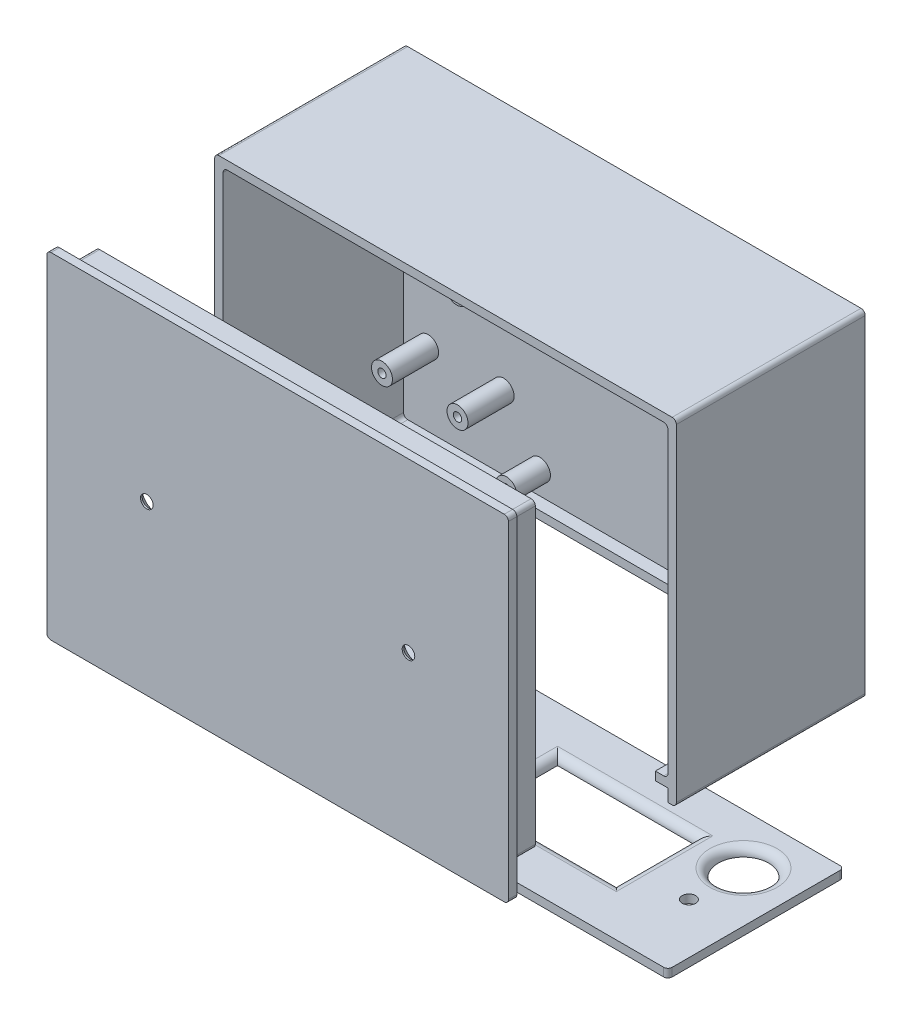
SolidWorks part; units mm, degrees
ref_plane "Спереди" through (0, 0, 0) normal (0, 0, 1) x (1, 0, 0)
ref_plane "Сверху" through (0, 0, 0) normal (0, 1, 0) x (1, 0, 0)
ref_plane "Справа" through (0, 0, 0) normal (1, 0, 0) x (0, 0, -1)
sketch "Эскиз1" plane through (0, 0, 0) normal (0, 0, 1) x (1, 0, 0)
  line L0 (-55, -41.511) -> (-53, -41.511)
  line L2 (-55, 38.489) -> (-55, -41.511)
  line L5 (-55, 38.489) -> (55, 38.489)
  line L6 (53, -36.511) -> (53, 36.489)
  line L7 (-53, -41.511) -> (-53, -38.511)
  line L8 (-53, -38.511) -> (-50, -38.511)
  line L9 (-50, -38.511) -> (-50, -36.511)
  line L10 (-50, -36.511) -> (-53, -36.511)
  line L11 (-53, -36.511) -> (-53, 36.489)
  line L12 (-53, 36.489) -> (53, 36.489)
  line L13 (0, 55.7111) -> (0, -96.3987) construction
  line L14 (50, -36.511) -> (53, -36.511)
  line L15 (50, -38.511) -> (50, -36.511)
  line L16 (53, -38.511) -> (50, -38.511)
  line L17 (53, -41.511) -> (53, -38.511)
  line L18 (55, 38.489) -> (55, -41.511)
  line L19 (55, -41.511) -> (53, -41.511)
  point P0 (0, 0)
  point P15 (0, 36.489)
  point P21 (0, 38.489)
  dimension "D1" = 2
  dimension "D2" = 2
  dimension "D3" = 2
  dimension "D4" = 55
  dimension "D5" = 80
  dimension "D6" = 2
  dimension "D7" = 3
  dimension "D8" = 3
extrude "Бобышка-Вытянуть3" add sketch "Эскиз1" along normal blind 43
sketch "Эскиз2" plane through (0, 0, 0) normal (0, 0, -1) x (-1, 0, 0)
  line L36 (55, 38.489) -> (55, -41.511) construction
  line L37 (-55, 38.489) -> (55, 38.489) construction
  line L38 (-55, -41.511) -> (-55, 38.489) construction
  line L39 (55, 38.489) -> (55, -41.511)
  line L40 (-55, 38.489) -> (55, 38.489)
  line L41 (-55, -41.511) -> (-55, 38.489)
  line L42 (-55, -41.511) -> (55, -41.511)
extrude "Бобышка-Вытянуть4" add sketch "Эскиз2" along normal blind 2
ref_plane "Плоскость1" through (0, 0, 8) normal (0, 0, 1) x (1, 0, 0)
sketch "Эскиз3" plane through (0, 0, 8) normal (0, 0, 1) x (1, 0, 0)
  line L0 (-53, -38.511) -> (-50, -38.511) construction
  line L1 (48, -32.511) -> (-23, -32.511) construction
  line L2 (48, -32.511) -> (48, 17.489) construction
  line L3 (48, 17.489) -> (-23, 17.489) construction
  line L4 (-23, -32.511) -> (-23, 17.489) construction
  line L5 (-33.1063, -7.511) -> (53.7568, -7.511) construction
  line L6 (12.5, 27.0434) -> (12.5, -35.2357) construction
  line L8 (50, -38.511) -> (53, -38.511) construction
  line L9 (53, 36.489) -> (53, -36.511) construction
  line L10 (-38.1409, 10.489) -> (-38.1409, -27.511) construction
  line L11 (-49.1409, 10.489) -> (-27.1409, 10.489) construction
  line L12 (-49.1409, 10.489) -> (-49.1409, -27.511) construction
  line L13 (-49.1409, -27.511) -> (-27.1409, -27.511) construction
  line L14 (-27.1409, 10.489) -> (-27.1409, -27.511) construction
  circle A0 centre (-20.5, 15.989) radius 1
  circle A1 centre (-20.5, 15.989) radius 2.5
  circle A2 centre (45.5, 15.989) radius 2.5
  circle A3 centre (45.5, 15.989) radius 1
  circle A4 centre (-20.5, 15.989) radius 1
  circle A5 centre (-20.5, 15.989) radius 2.5
  circle A6 centre (45.5, 15.989) radius 2.5
  circle A7 centre (45.5, 15.989) radius 1
  circle A8 centre (45.5, -31.011) radius 1
  circle A9 centre (45.5, -31.011) radius 2.5
  circle A10 centre (-20.5, -31.011) radius 2.5
  circle A11 centre (-20.5, -31.011) radius 1
  circle A12 centre (45.5, -31.011) radius 1
  circle A13 centre (45.5, -31.011) radius 2.5
  circle A14 centre (-20.5, -31.011) radius 2.5
  circle A15 centre (-20.5, -31.011) radius 1
  circle A16 centre (-47.1409, -19.011) radius 1
  circle A17 centre (-47.1409, -19.011) radius 2.5
  circle A18 centre (-29.1409, -19.011) radius 2.5
  circle A19 centre (-29.1409, -19.011) radius 1
  circle A20 centre (-29.3409, 6.489) radius 2.5
  circle A21 centre (-29.3409, 6.489) radius 1
  point P0 (12.5, -7.511)
  point P35 (12.5, 17.489)
  point P36 (-23, -7.511)
  point P40 (-38.1409, -8.8408)
  dimension "D5" = 2
  dimension "D6" = 5
  dimension "D11" = 2
  dimension "D12" = 5
  dimension "D1" = 50
  dimension "D2" = 71
  dimension "D3" = 6
  dimension "D4" = 5
  dimension "D7" = 47
  dimension "D8" = 66
  dimension "D9" = 38
  dimension "D10" = 22
  dimension "D13" = 8.5
  dimension "D14" = 18
  dimension "D15" = 4
  dimension "D16" = 2.2
  dimension "D17" = 11
extrude "Бобышка-Вытянуть2" add sketch "Эскиз3" against normal up to surface (8 mm away) contours A1 | A10 | A11 | A2 | A3 | A9 | A8 | A0 up to face at (0, -25.8443, 0)
sketch "Эскиз4" plane through (0, 0, 0) normal (0, 0, 1) x (1, 0, 0)
  line L0 (-50, -36.511) -> (-50, -38.511)
  line L1 (-50, -38.511) -> (50, -38.511)
  line L2 (50, -38.511) -> (50, -36.511)
  line L3 (50, -36.511) -> (-50, -36.511)
extrude "Бобышка-Вытянуть5" add sketch "Эскиз4" along normal blind 3
ref_plane "Плоскость2" through (0, 0, 83) normal (0, 0, 1) x (1, 0, 0)
sketch "Эскиз5" plane through (0, 0, 83) normal (0, 0, 1) x (1, 0, 0)
  line L0 (55, -41.511) -> (55, 38.489) construction
  line L1 (55, 38.489) -> (-55, 38.489) construction
  line L2 (-55, 38.489) -> (-55, -41.511) construction
  line L3 (55, -41.511) -> (55, 38.489)
  line L4 (55, 38.489) -> (-55, 38.489)
  line L5 (-55, 38.489) -> (-55, -41.511)
  line L6 (-55, -41.511) -> (55, -41.511)
  line L7 (-55, -1.511) -> (66.1555, -1.511) construction
  line L8 (0, 36.489) -> (0, -47.4003) construction
  line L9 (-53, 36.489) -> (53, 36.489) construction
  circle A0 centre (-31.1737, -1.511) radius 1.5
  circle A1 centre (31.1737, -1.511) radius 1.5
  dimension "D1" = 3
extrude "Бобышка-Вытянуть6" add sketch "Эскиз5" against normal blind 2 separate body
sketch "Эскиз6" plane through (0, 0, 83) normal (0, 0, 1) x (1, 0, 0)
  line L0 (-50.4, 33.889) -> (50.4, 33.889)
  line L1 (50.4, 33.889) -> (50.4, -33.911)
  line L2 (50.4, -33.911) -> (50, -33.911)
  line L3 (0, 55.7111) -> (0, -96.3987) construction
  line L4 (50, -33.911) -> (50, -35.911)
  line L5 (49.6, -36.511) -> (49.6, -38.511)
  line L6 (-49.6, -38.511) -> (-49.6, -36.511)
  line L24 (-50, -35.911) -> (-50, -33.911)
  line L25 (-50, -33.911) -> (-50.4, -33.911)
  line L26 (-50.4, -33.911) -> (-50.4, 33.889)
  line L31 (52.4, -35.911) -> (50, -35.911)
  line L32 (52.4, 35.889) -> (52.4, -35.911)
  line L33 (-52.4, 35.889) -> (52.4, 35.889)
  line L34 (49.6, -36.511) -> (-49.6, -36.511)
  line L35 (-49.6, -38.511) -> (49.6, -38.511)
  line L36 (-52.4, -35.911) -> (-52.4, 35.889)
  line L37 (-50, -35.911) -> (-52.4, -35.911)
  line L38 (52.4, -35.911) -> (50, -35.911)
  line L39 (52.4, 35.889) -> (52.4, -35.911)
  line L40 (-52.4, 35.889) -> (52.4, 35.889)
  line L41 (-52.4, -35.911) -> (-52.4, 35.889)
  line L42 (-50, -35.911) -> (-52.4, -35.911)
  point P0 (0, -38.511)
  dimension "D1" = 99.2
  dimension "D3" = 2
  dimension "D4" = 2
  dimension "D5" = 2
  dimension "D6" = 2
  dimension "D7" = 2
  dimension "D2" = 0.6
extrude "Бобышка-Вытянуть7" add sketch "Эскиз6" against normal blind 9 contours L42 L24 L25 L26 L0 L1 L2 L4 L38 L39 L40 L41 region at (-51.6704, -0.011, 83)
extrude "Бобышка-Вытянуть8" add sketch "Эскиз6<3>" against normal blind 5 contours L6 L35 L5 L34 region at (0, -37.511, 83)
sketch "Эскиз6<3>" plane through (0, 0, 83) normal (0, 0, 1) x (1, 0, 0) same geometry as "Эскиз6"
ref_plane "Плоскость3" through (0, -78.511, 0) normal (0, -1, 0) x (-1, 0, 0)
sketch "Эскиз10" plane through (0, -78.511, 0) normal (0, -1, 0) x (-1, 0, 0)
  line L0 (-28.2241, -21.0368) -> (29.3686, -21.0368) construction
  line L1 (15, -14) -> (19.5, -14)
  line L2 (15, -14) -> (15, -19.5)
  line L3 (15, -19.5) -> (19.5, -19.5)
  line L4 (50, -43) -> (50, -3) construction
  line L5 (-50, -3) -> (50, -3) construction
  line L6 (-50, -3) -> (-50, -39.3) construction
  line L7 (-50, -39.3) -> (50, -39.3) construction
  line L8 (-52.5, -42.5) -> (52.5, -42.5)
  line L9 (52.5, -42.5) -> (52.5, -0.5)
  line L10 (52.5, -0.5) -> (-52.5, -0.5)
  line L11 (-52.5, -0.5) -> (-52.5, -42.5)
  line L12 (-52.5, -42.5) -> (52.5, -42.5)
  line L13 (52.5, -42.5) -> (52.5, -0.5)
  line L14 (52.5, -0.5) -> (-52.5, -0.5)
  line L15 (-52.5, -0.5) -> (-52.5, -42.5)
  line L16 (50, -3) -> (50, -39.3) construction
  line L17 (-50, -3) -> (50, -39.3) construction
  line L18 (-50, -39.3) -> (50, -3) construction
  line L19 (19.5, -14) -> (19.5, -19.5)
  line L20 (-28.2241, -11.5368) -> (4.7759, -11.5368)
  line L21 (-28.2241, -11.5368) -> (-28.2241, -30.5368)
  line L22 (-28.2241, -30.5368) -> (4.7759, -30.5368)
  line L23 (4.7759, -11.5368) -> (4.7759, -30.5368)
  circle A0 centre (-40.5, -12.5) radius 6
  circle A1 centre (-40.5, -25.5) radius 1.6
  point P4 (0, -21.15)
  dimension "D3" = 12
  dimension "D6" = 3.2
  dimension "D2" = 3.2
  dimension "D4" = 12
  dimension "D5" = 12
  dimension "D7" = 25
  dimension "D8" = 12
  dimension "D9" = 4.5
  dimension "D10" = 5.5
  dimension "D11" = 33
  dimension "D12" = 23
  dimension "D13" = 19
  dimension "D14" = 33
  dimension "D1" = 0.5
extrude "Бобышка-Вытянуть9" add sketch "Эскиз10" against normal blind 2 separate body
chamfer "Фаска1" distance 1.6 angle 45 2 edges at (29.6737, -1.511, 81) (-29.6737, -1.511, 81)
fillet "Скругление1" radius 1 8 edges at (-53, -36.511, 21.5) (-53, 36.489, 21.5) (53, 36.489, 21.5) (53, -36.511, 21.5) (-55, -41.511, 20.5) (55, -41.511, 20.5) (55, 38.489, 20.5) (-55, 38.489, 20.5)
fillet "Скругление2" radius 1 10 edges at (-55, -41.511, 82) (55, -41.511, 82) (55, 38.489, 82) (-55, 38.489, 82) (52.4, 35.889, 77.5) (50, -35.911, 77.5) (52.4, -35.911, 77.5) (-50, -35.911, 77.5) (-52.4, -35.911, 77.5) (-52.4, 35.889, 77.5)
fillet "Скругление3" radius 1 4 edges at (-52.5, -77.511, 0.5) (-52.5, -77.511, 42.5) (52.5, -77.511, 42.5) (52.5, -77.511, 0.5)
extrude "Бобышка-Вытянуть10" add sketch "Эскиз3<3>" against normal up to surface (10 mm away) from offset 3 contours A17 | A16 | A19 | A18 | A20 | A21 up to face at (0, -1.511, -2)
sketch "Эскиз3<3>" plane through (0, 0, 8) normal (0, 0, 1) x (1, 0, 0) same geometry as "Эскиз3"
fillet "Скругление4" radius 2 9 edges at (-17.25, -76.511, 14) (-15, -76.511, 16.75) (-17.25, -76.511, 19.5) (-19.5, -76.511, 16.75) (28.2241, -76.511, 21.0368) (11.7241, -76.511, 30.5368) (-4.7759, -76.511, 21.0368) (11.7241, -76.511, 11.5368) (40.5, -76.511, 6.5)
equation "\"D5@Эскиз6\"=\"D4@Эскиз6\""
equation "\"D6@Эскиз6\"=\"D4@Эскиз6\""
equation "\"D7@Эскиз6\"=\"D4@Эскиз6\""
equation "\"D3@Эскиз6\"=\"D4@Эскиз6\""
